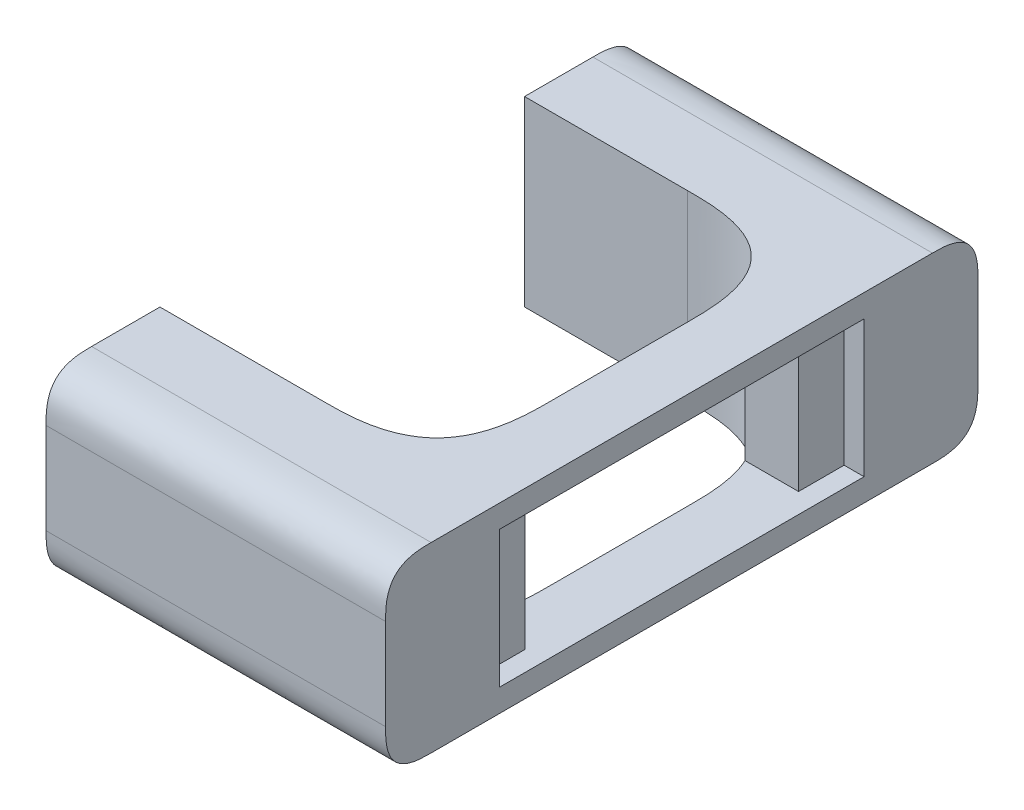
SolidWorks part; units mm, degrees
ref_plane "Front Plane" through (0, 0, 0) normal (0, 0, 1) x (1, 0, 0)
ref_plane "Top Plane" through (0, 0, 0) normal (0, 1, 0) x (1, 0, 0)
ref_plane "Right Plane" through (0, 0, 0) normal (1, 0, 0) x (0, 0, -1)
sketch "Sketch2" plane through (0, 0, 0) normal (1, 0, 0) x (0, 0, -1)
  line L1 (26, -8) -> (-26, -8)
  line L2 (26, -8) -> (26, 8)
  line L3 (26, 8) -> (-26, 8)
  line L4 (-26, -8) -> (-26, 8)
  line L5 (26, -8) -> (-26, 8) construction
  line L6 (26, 8) -> (-26, -8) construction
  line L7 (16, -6) -> (-16, -6)
  line L8 (16, -6) -> (16, 6)
  line L9 (16, 6) -> (-16, 6)
  line L10 (-16, -6) -> (-16, 6)
  line L11 (16, -6) -> (-16, 6) construction
  line L12 (16, 6) -> (-16, -6) construction
  point P0 (0, 0)
  point P6 (0, 0)
  point P11 (-20.2068, 11.2444)
  dimension "D1" = 12
  dimension "D2" = 32
  dimension "D3" = 2
  dimension "D4" = 10
extrude "Boss-Extrude1" add sketch "Sketch2" along normal blind 5.5
sketch "Sketch3" plane through (5.5, 0, 0) normal (1, 0, 0) x (0, 0, -1)
  line L0 (-16, -6) -> (16, -6) construction
  line L1 (-16, 6) -> (-12, 6)
  line L2 (-16, 6) -> (-16, -6)
  line L3 (-16, -6) -> (-12, -6)
  line L4 (-12, 6) -> (-12, -6)
  line L6 (16, 6) -> (12, 6)
  line L7 (16, 6) -> (16, -6)
  line L8 (16, -6) -> (12, -6)
  line L9 (12, 6) -> (12, -6)
  dimension "D1" = 4
  dimension "D2" = 4
extrude "Boss-Extrude2" add sketch "Sketch3" against normal up to surface (5.5 mm away) from offset 1.75 up to face at (0, 0, 0) offset against normal yes
sketch "Sketch4" plane through (0, 0, 0) normal (-1, 0, 0) x (0, 0, 1)
  line L0 (26, -8) -> (-26, -8) construction
  line L1 (-26, 8) -> (-16, 8)
  line L2 (-26, 8) -> (-26, -8)
  line L3 (-26, -8) -> (-16, -8)
  line L4 (-16, 8) -> (-16, -8)
  line L6 (26, 8) -> (16, 8)
  line L7 (26, 8) -> (26, -8)
  line L8 (26, -8) -> (16, -8)
  line L9 (16, 8) -> (16, -8)
  dimension "D1" = 10
  dimension "D2" = 10
extrude "Boss-Extrude3" add sketch "Sketch4" along normal blind 24.3
fillet "Fillet1" radius 10 2 edges at (0, 0, -16) (0, 0, 16) curvature continuous yes
fillet "Fillet2" radius 4 4 edges at (-9.4, 8, 26) (-9.4, -8, 26) (-9.4, 8, -26) (-9.4, -8, -26) curvature continuous yes
